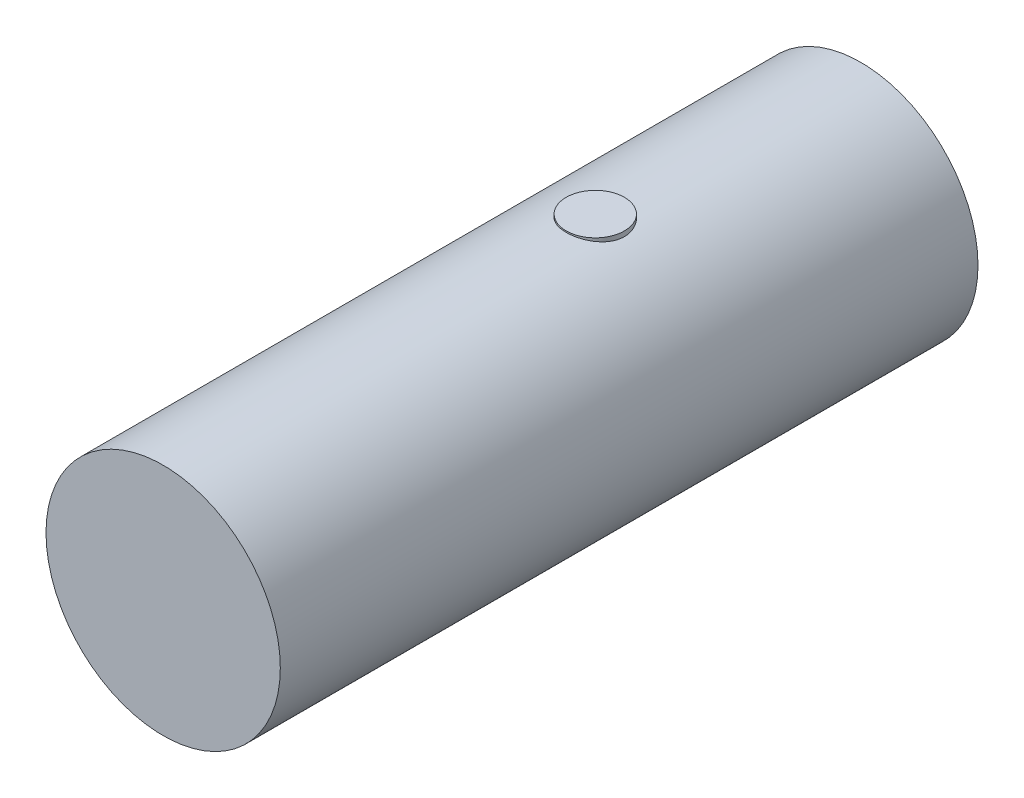
SolidWorks part; units mm, degrees
ref_plane "Ebene vorne" through (0, 0, 0) normal (0, 0, 1) x (1, 0, 0)
ref_plane "Ebene oben" through (0, 0, 0) normal (0, 1, 0) x (1, 0, 0)
ref_plane "Ebene rechts" through (0, 0, 0) normal (1, 0, 0) x (0, 0, -1)
sketch "Skizze1" plane through (0, 0, 0) normal (0, 0, 1) x (1, 0, 0)
  circle A0 centre (0, 0) radius 89
  dimension "D1" = 178
extrude "Aufsatz-Linear austragen1" add sketch "Skizze1" along normal blind 530
sketch "Skizze2" plane through (0, 0, 0) normal (0, 1, 0) x (1, 0, 0)
  line L0 (0, 0) -> (0, -530) construction
  line L1 (-89, -530) -> (89, -530) construction
  circle A0 centre (0, -201.7101) radius 22.1266
  point P7 (0, -224.2041)
  point P8 (0, -172.8284)
  point P9 (0, -241.5968)
  point P10 (0, -201.7101)
extrude "Aufsatz-Linear austragen2" add sketch "Skizze2" along normal blind 90 and the other way blind 90
